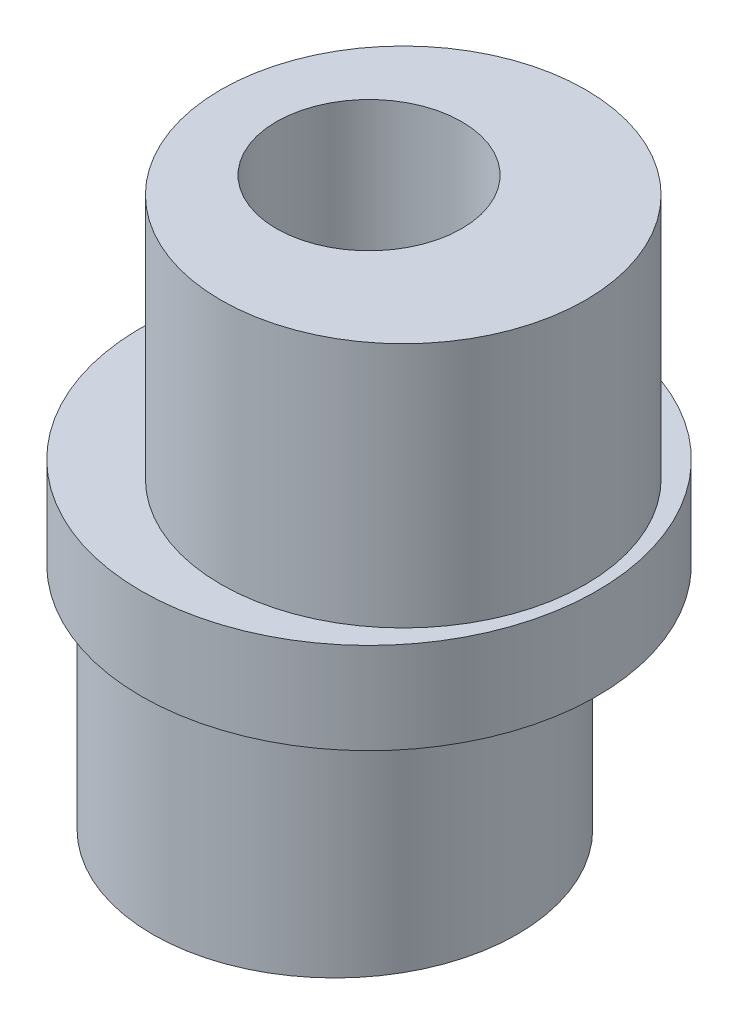
SolidWorks part; units mm, degrees
ref_plane "Front Plane" through (0, 0, 0) normal (0, 0, 1) x (1, 0, 0)
ref_plane "Top Plane" through (0, 0, 0) normal (0, 1, 0) x (1, 0, 0)
ref_plane "Right Plane" through (0, 0, 0) normal (1, 0, 0) x (0, 0, -1)
sketch "Sketch1" plane through (0, 0, 0) normal (0, 1, 0) x (1, 0, 0)
  circle A1 centre (0, 0) radius 7.5
  point P6 (0, 0)
  point P7 (0, 0)
  dimension "D1" = 15
extrude "Boss-Extrude1" add sketch "Sketch1" along normal blind 3 contours A1
sketch "Sketch2" plane through (0, 3, 0) normal (0, 1, 0) x (1, 0, 0)
  circle A0 centre (1.125, 0) radius 6
  circle A1 centre (0, 0) radius 7.5 construction
  dimension "D1" = 12
  dimension "D2" = 1.125
extrude "Boss-Extrude2" add sketch "Sketch2" along normal blind 8.1
sketch "Sketch3" plane through (0, 0, 0) normal (0, -1, 0) x (1, 0, 0)
  circle A0 centre (-1.125, 0) radius 6
  point P2 (0, 0)
  point P4 (0, 0)
  dimension "D1" = 12
  dimension "D2" = 1.125
extrude "Boss-Extrude3" add sketch "Sketch3" along normal blind 8.1
sketch "Sketch4" plane through (0, 11.1, 0) normal (0, 1, 0) x (1, 0, 0)
  circle A0 centre (0, 0) radius 3.05
  dimension "D1" = 6.1
extrude "Cut-Extrude1" cut sketch "Sketch4" against normal blind 24.1
